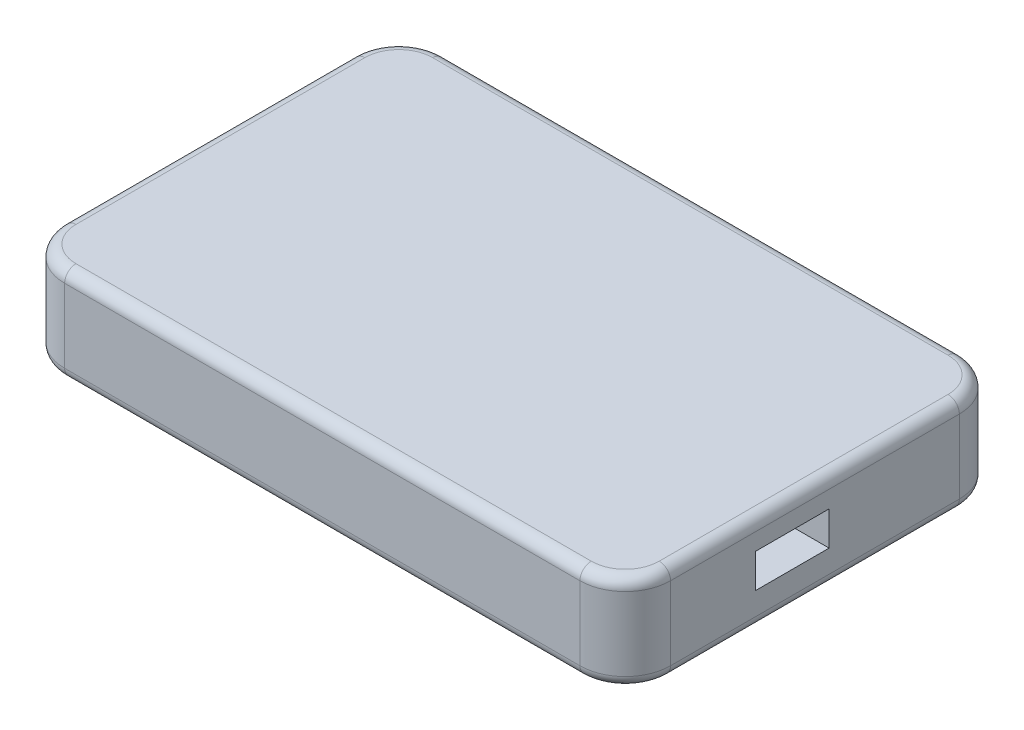
SolidWorks part; units mm, degrees
ref_plane "Front Plane" through (0, 0, 0) normal (0, 0, 1) x (1, 0, 0)
ref_plane "Top Plane" through (0, 0, 0) normal (0, 1, 0) x (1, 0, 0)
ref_plane "Right Plane" through (0, 0, 0) normal (1, 0, 0) x (0, 0, -1)
sketch "Sketch1" plane through (0, 0, 0) normal (1, 0, 0) x (0, 0, -1)
  line L1 (0, 0) -> (67, 0)
  line L2 (0, 0) -> (0, 17)
  line L3 (0, 17) -> (67, 17)
  line L4 (67, 0) -> (67, 17)
  dimension "D1" = 17
  dimension "D2" = 67
extrude "Boss-Extrude1" add sketch "Sketch1" along normal mid plane 107
fillet "Fillet1" radius 2 8 edges at (-53.5, 0, -33.5) (-53.5, 17, -33.5) (53.5, 0, -33.5) (53.5, 17, -33.5) (0, 0, -67) (0, 0, 0) (0, 17, -67) (0, 17, 0)
fillet "Fillet2" radius 8 12 edges at (-52.9142, 0.5858, -0.5858) (-52.9142, 16.4142, -0.5858) (52.9142, 0.5858, -0.5858) (52.9142, 16.4142, -0.5858) (52.9142, 16.4142, -66.4142) (52.9142, 0.5858, -66.4142) (-52.9142, 16.4142, -66.4142) (-52.9142, 0.5858, -66.4142) (-53.5, 8.5, -67) (53.5, 8.5, -67) (53.5, 8.5, 0) (-53.5, 8.5, 0)
sketch "Sketch2" plane through (53.5, 0, 0) normal (1, 0, 0) x (0, 0, -1)
  line L0 (0, 2) -> (0, 15) construction
  line L1 (23, 12) -> (36, 12)
  line L2 (23, 12) -> (23, 6)
  line L3 (23, 6) -> (36, 6)
  line L4 (36, 12) -> (36, 6)
  line L5 (8, 17) -> (59, 17) construction
  point P8 (29.5, 12)
  dimension "D1" = 6
  dimension "D2" = 13
  dimension "D3" = 23
  dimension "D4" = 5
extrude "Cut-Extrude1" cut sketch "Sketch2" against normal blind 8
